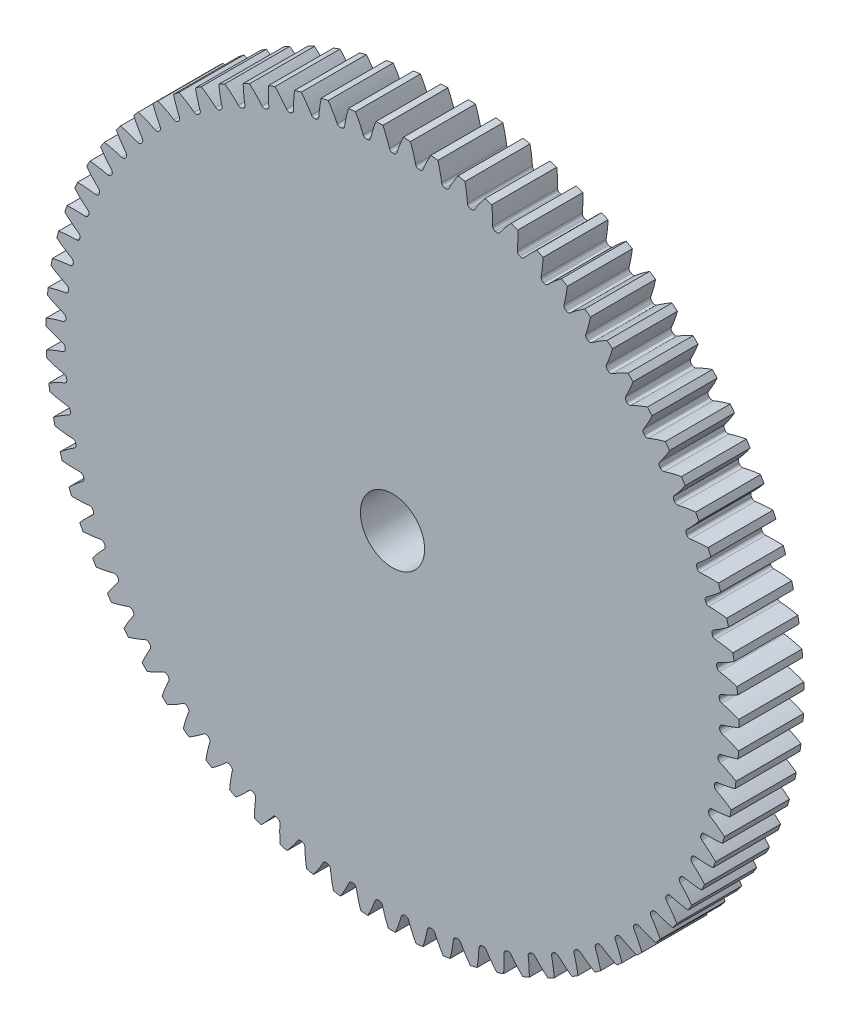
SolidWorks part; units mm, degrees
ref_plane "Front" through (0, 0, 0) normal (0, 0, 1) x (1, 0, 0)
ref_plane "Top" through (0, 0, 0) normal (0, 1, 0) x (1, 0, 0)
ref_plane "Right" through (0, 0, 0) normal (1, 0, 0) x (0, 0, -1)
sketch "Sketch3" plane through (0, 0, 0) normal (0, 0, 1) x (1, 0, 0)
  circle A0 centre (0, 0) radius 51.435
  dimension "od" = 102.87
extrude "gearBody" add sketch "Sketch3" along normal blind 9.652
sketch "Sketch2" plane through (0, 0, 0) normal (0, 0, 1) x (1, 0, 0)
  line L0 (0, 0) -> (43.5514, 18.0396) construction
  line L1 (59.1443, -9.7382) -> (0, 0) construction
  line L2 (0, 0) -> (36.3143, 0) construction
  line L3 (50.1649, -0.1132) -> (50.1222, -2.0716) construction
  line L5 (50.1435, -1.0924) -> (0, 0) construction
  line L7 (0, 0) -> (47.1397, 0) construction
  arc A0 (47.1302, -0.9461) -> (47.1267, -1.1074) centre (0, 0) ccw construction
  arc A1 (51.4334, 0.4005) -> (51.3672, -2.6401) centre (0, 0) ccw construction
  arc A2 (50.1649, -0.1132) -> (50.1222, -2.0716) centre (0, 0) ccw construction
  arc A3 (48.5768, -1.1406) -> (48.5804, -0.976) centre (0, 0) ccw
  arc A4 (59.1443, -9.7382) -> (48.9095, -1.6159) centre (42.7244, -19.9191) ccw
  arc A5 (59.1443, -9.7382) -> (59.5123, 7.1533) centre (0, 0) ccw
  arc A6 (59.5123, 7.1533) -> (48.9335, -0.5156) centre (43.5514, 18.0396) cw
  arc A7 (48.5804, -0.976) -> (48.9335, -0.5156) centre (49.0699, -0.9858) cw
  arc A8 (48.9095, -1.6159) -> (48.5768, -1.1406) centre (49.0663, -1.1521) cw
  point P6 (59.5123, 7.1533)
  point P22 (59.1443, -9.7382)
  dimension "baseDia" = 94.2794
  dimension "od" = 102.87
  dimension "pd" = 100.33
  dimension "rd" = 97.1804
  dimension "rFillet" = 0.4896
  dimension "pointX" = 59.5123
  dimension "pointY" = 7.1533
  dimension "CTT" = 1.9583
  dimension "flankCenterAngle" = 22.5
extrude "toothCut" cut sketch "Sketch2" along normal through all
pattern_circular "CirPattern1" count 79 over 360 about axis through (0, 0, 9.652) along (0, 0, -1) of "toothCut"
sketch "hub1Dia" plane through (0, 0, 0) normal (0, 0, -1) x (-1, 0, 0)
  circle A0 centre (0, 0) radius 12.7
  dimension "hub1Dia" = 25.4
sketch "hub2Dia" plane through (0, 0, 9.652) normal (0, 0, 1) x (1, 0, 0)
  circle A0 centre (0, 0) radius 12.7
  dimension "hub2dia" = 25.4
sketch "boreDia" plane through (0, 0, 0) normal (0, 0, 1) x (1, 0, 0)
  circle A0 centre (0, 0) radius 4.7625
  dimension "boreDia" = 9.525
extrude "bore" cut sketch "boreDia" against normal mid plane 25400
